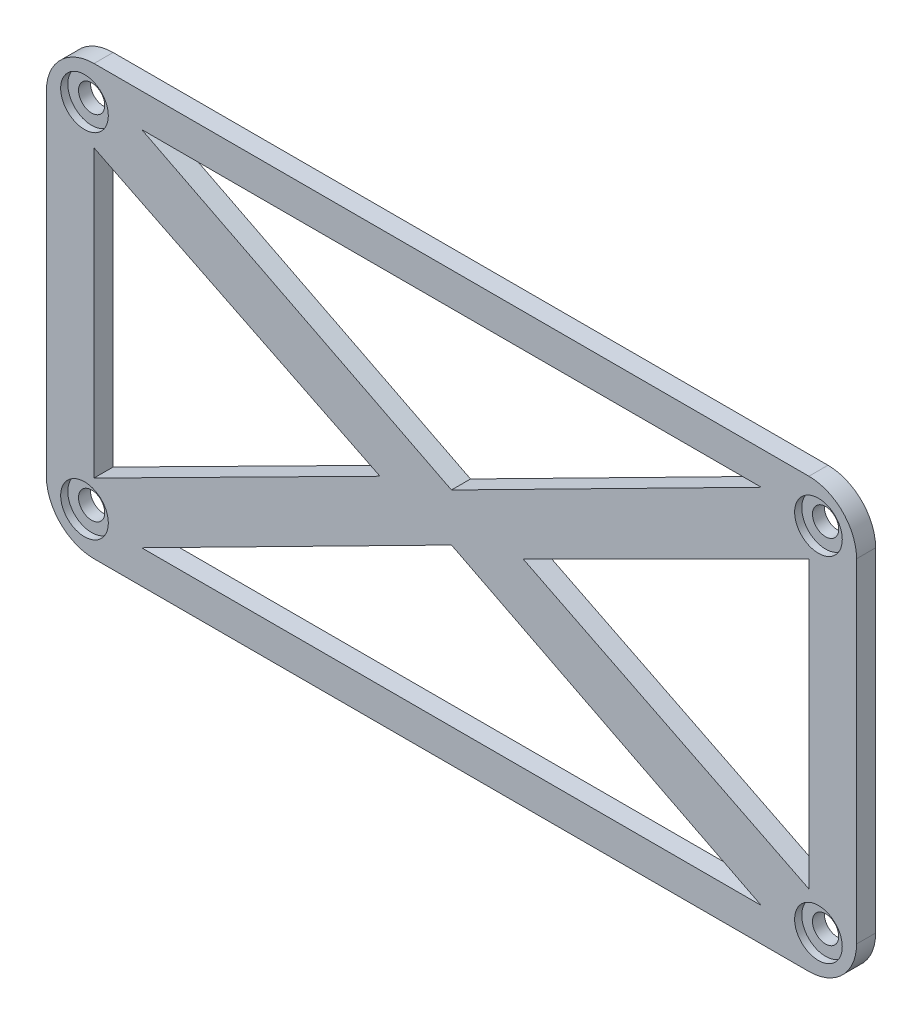
SolidWorks part; units mm, degrees
ref_plane "前视基准面" through (0, 0, 0) normal (0, 0, 1) x (1, 0, 0)
ref_plane "上视基准面" through (0, 0, 0) normal (0, 1, 0) x (1, 0, 0)
ref_plane "右视基准面" through (0, 0, 0) normal (1, 0, 0) x (0, 0, -1)
sketch "草图1" plane through (0, 0, 0) normal (0, 0, 1) x (1, 0, 0)
  line L1 (-72.5741, 45.4874) -> (77.4259, 45.4874)
  line L2 (-82.5741, 35.4874) -> (-82.5741, -34.5126)
  line L3 (-72.5741, -44.5126) -> (77.4259, -44.5126)
  line L4 (87.4259, 35.4874) -> (87.4259, -34.5126)
  arc A0 (-72.5741, 45.4874) -> (-82.5741, 35.4874) centre (-72.5741, 35.4874) ccw
  arc A1 (-72.5741, -44.5126) -> (-82.5741, -34.5126) centre (-72.5741, -34.5126) cw
  arc A2 (87.4259, 35.4874) -> (77.4259, 45.4874) centre (77.4259, 35.4874) ccw
  arc A3 (87.4259, -34.5126) -> (77.4259, -44.5126) centre (77.4259, -34.5126) cw
  dimension "D1" = 10
  dimension "D2" = 10
  dimension "D3" = 10
  dimension "D4" = 10
  dimension "D5" = 90
  dimension "D6" = 170
extrude "凸台-拉伸1" add sketch "草图1" along normal blind 4
ref_plane "for screw hole" through (0, 0, 4) normal (0, 0, 1) x (1, 0, 0)
sketch "草图2" plane through (0, 0, 4) normal (0, 0, 1) x (1, 0, 0)
  line L0 (77.4259, 45.4874) -> (-72.5741, 45.4874) construction
  line L1 (-82.5741, 35.4874) -> (-82.5741, -34.5126) construction
  line L2 (-72.5741, -44.5126) -> (77.4259, -44.5126) construction
  line L3 (87.4259, -34.5126) -> (87.4259, 35.4874) construction
  line L4 (-62.5741, 38.4874) -> (2.4259, 5.4874)
  line L6 (-72.5741, 30.1561) -> (-12.5741, 0.4874)
  line L8 (2.4259, -4.5126) -> (-62.5741, -37.5126)
  line L10 (67.4259, -37.5126) -> (2.4259, -4.5126)
  line L12 (-72.5741, -29.8439) -> (-12.5741, 0.4874)
  line L13 (-72.5741, 30.1561) -> (-72.5741, -29.8439)
  line L15 (-62.5741, -37.5126) -> (67.4259, -37.5126)
  line L17 (67.4259, 38.4874) -> (2.4259, 5.4874)
  line L19 (-62.5741, 38.4874) -> (67.4259, 38.4874)
  line L21 (17.4259, 0.4874) -> (77.4259, 30.4874)
  line L25 (17.4259, 0.4874) -> (77.4259, -29.5126)
  line L26 (77.4259, -29.5126) -> (77.4259, 30.4874)
  circle A0 centre (-74.5741, 37.4874) radius 2.75
  circle A1 centre (-74.5741, -36.5126) radius 2.75
  circle A2 centre (79.4259, 37.4874) radius 2.75
  circle A3 centre (79.4259, -36.5126) radius 2.75
  point P19 (-62.5741, 30.4874)
  point P23 (77.4259, 30.4874)
  point P38 (2.4259, 5.4874)
  point P39 (-12.5741, 0.4874)
  point P40 (67.4259, 38.4874)
  point P41 (-62.5741, 38.4874)
  point P42 (2.4259, -4.5126)
  point P43 (17.4259, 0.4874)
  point P45 (-72.5741, -29.8439)
  point P46 (-62.5741, -37.5126)
  point P47 (67.4259, -37.5126)
  point P48 (77.4259, -29.5126)
  dimension "D2" = 5.5
  dimension "D3" = 5.5
  dimension "D4" = 5.5
  dimension "D8" = 8
  dimension "D9" = 8
  dimension "D10" = 8
  dimension "D11" = 5.5
  dimension "D14" = 70
  dimension "D5" = 8
  dimension "D6" = 8
  dimension "D7" = 8
  dimension "D12" = 8
  dimension "D13" = 8
  dimension "D15" = 70
  dimension "D16" = 40
  dimension "D17" = 45
  dimension "D18" = 45
  dimension "D19" = 60
  dimension "D20" = 7
  dimension "D21" = 7
  dimension "D22" = 20
  dimension "D23" = 20
  dimension "D24" = 20
  dimension "D25" = 10
  dimension "D26" = 7
  dimension "D27" = 20
  dimension "D28" = 15
  dimension "D29" = 15
  dimension "D30" = 10
  dimension "D31" = 10
  dimension "D32" = 15
  dimension "D33" = 7
  dimension "D34" = 20
extrude "切除-拉伸1" cut sketch "草图2" against normal blind 10 and the other way blind 39
ref_plane "for outer screw hole" through (0, 0, 4) normal (0, 0, 1) x (1, 0, 0)
sketch "草图3" plane through (0, 0, 4) normal (0, 0, 1) x (1, 0, 0)
  circle A0 centre (-74.5741, 37.4874) radius 5
  circle A1 centre (79.4259, 37.4874) radius 5
  circle A2 centre (79.4259, -36.5126) radius 5
  circle A3 centre (-74.5741, -36.5126) radius 5
  dimension "D1" = 10
  dimension "D2" = 10
  dimension "D3" = 10
  dimension "D4" = 10
extrude "切除-拉伸2" cut sketch "草图3" against normal blind 1.5
ref_plane "for stands" through (0, 0, 4) normal (0, 0, 1) x (1, 0, 0)
